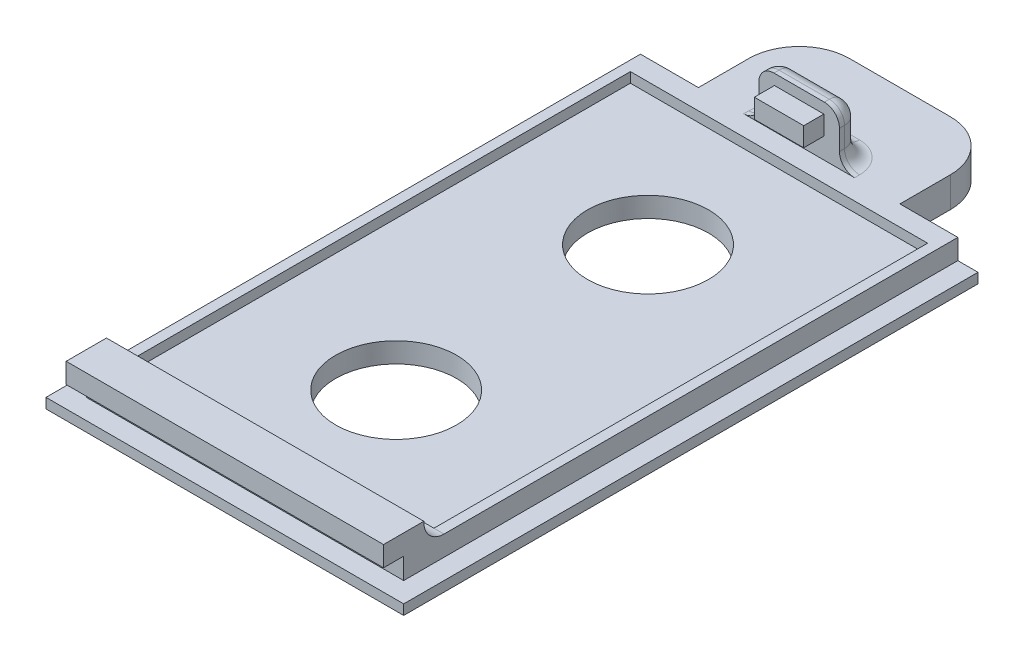
SolidWorks part; units mm, degrees
ref_plane "Plan de face" through (0, 0, 0) normal (0, 0, 1) x (1, 0, 0)
ref_plane "Plan de dessus" through (0, 0, 0) normal (0, 1, 0) x (1, 0, 0)
ref_plane "Plan de droite" through (0, 0, 0) normal (1, 0, 0) x (0, 0, -1)
sketch "Esquisse1" plane through (0, 0, 0) normal (0, 0, 1) x (1, 0, 0)
  line L0 (0, 0) -> (-2, 0)
  line L2 (0, 0) -> (0, 2)
  line L3 (0, 2) -> (31.5, 2)
  line L4 (31.5, 0) -> (31.5, 2)
  line L5 (-2, 0) -> (-2, -1)
  line L6 (-2, -1) -> (33.5, -1)
  line L7 (33.5, -1) -> (33.5, 0)
  line L8 (33.5, 0) -> (31.5, 0)
  dimension "D1" = 2
  dimension "D2" = 31.5
  dimension "D3" = 2
  dimension "D4" = 1
extrude "Boss.-Extru.1" add sketch "Esquisse1" along normal blind 55
sketch "Esquisse2" plane through (0, -1, 0) normal (0, -1, 0) x (1, 0, 0)
  line L0 (-2, 55) -> (-2, 0) construction
  line L1 (-2, 57) -> (33.5, 57)
  line L2 (-2, 57) -> (-2, 55)
  line L3 (-2, 55) -> (33.5, 55)
  line L4 (33.5, 57) -> (33.5, 55)
  line L5 (-2, 55) -> (33.5, 55) construction
  dimension "D1" = 2
extrude "Boss.-Extru.2" add sketch "Esquisse2" against normal blind 1
sketch "Esquisse3" plane through (0, 0, 0) normal (-1, 0, 0) x (0, 0, 1)
  line L0 (55, 2) -> (55, 2.1)
  line L1 (55, 2.1) -> (57, 2.1)
  line L2 (57, 2.1) -> (57, 4.1)
  line L3 (57, 4.1) -> (53, 4.1)
  line L4 (53, 4.1) -> (53, 2)
  line L5 (55, 2) -> (0, 2) construction
  line L6 (53, 2) -> (55, 2)
  line L7 (55, 2) -> (55, 0) construction
  dimension "D1" = 2
  dimension "D2" = 2
  dimension "D3" = 0.1
  dimension "D4" = 2
extrude "Boss.-Extru.3" add sketch "Esquisse3" against normal up to surface (31.5 mm away) up to face at (31.5, 1, 27.5)
sketch "Esquisse4" plane through (0, 0, 0) normal (0, 0, -1) x (-1, 0, 0)
  line L2 (-19.75, 0.5) -> (-19.75, 7)
  line L3 (-19.75, 7) -> (-11.75, 7)
  line L4 (-11.75, 0.5) -> (-11.75, 7)
  line L7 (-19.75, 0.5) -> (-11.75, 0.5)
  line L9 (-31.5, 2) -> (0, 2) construction
  line L10 (-15.75, 0.5) -> (-15.75, -1) construction
  line L11 (2, -1) -> (-33.5, -1) construction
  dimension "D1" = 8
  dimension "D2" = 6.5
  dimension "D4" = 1.5
extrude "Boss.-Extru.4" add sketch "Esquisse4" along normal blind 2
sketch "Esquisse5" plane through (0, 0, 0) normal (0, 0, 1) x (1, 0, 0)
  line L0 (15.75, 5.95) -> (15.75, 7) construction
  line L1 (13.3, 5.95) -> (18.2, 5.95)
  line L2 (13.3, 5.95) -> (13.3, 4.05)
  line L3 (13.3, 4.05) -> (18.2, 4.05)
  line L4 (18.2, 5.95) -> (18.2, 4.05)
  line L5 (11.75, 7) -> (19.75, 7) construction
  line L6 (33.5, 0) -> (-2, 0) construction
  point P8 (13.3, 5)
  dimension "D1" = 1.9
  dimension "D2" = 4.9
  dimension "D3" = 5
extrude "Boss.-Extru.5" add sketch "Esquisse5" along normal blind 2
sketch "Esquisse6" plane through (0, -1, 0) normal (0, -1, 0) x (1, 0, 0)
  line L0 (5.75, 0) -> (5.75, -5)
  line L1 (-2, 0) -> (33.5, 0) construction
  line L2 (25.75, -5) -> (25.75, 0)
  line L3 (25.75, 0) -> (5.75, 0)
  line L4 (10.75, -10) -> (20.75, -10)
  arc A1 (20.75, -10) -> (25.75, -5) centre (20.75, -5) ccw
  arc A2 (10.75, -10) -> (5.75, -5) centre (10.75, -5) cw
  point P6 (15.75, 0)
  dimension "D2" = 5
  dimension "D1" = 5
  dimension "D3" = 20
extrude "Boss.-Extru.6" add sketch "Esquisse6" against normal up to surface (3 mm away) up to face at (15.75, 2, 17.6667)
sketch "Esquisse8" plane through (0, 2, 0) normal (0, 1, 0) x (1, 0, 0)
  line L0 (31.5, -53) -> (31.5, 0) construction
  line L1 (1, -51) -> (30.5, -51)
  line L2 (1, -51) -> (1, -2)
  line L3 (1, -2) -> (30.5, -2)
  line L4 (30.5, -51) -> (30.5, -2)
  line L5 (0, -55) -> (0, 0) construction
  line L6 (31.5, -53) -> (0, -53) construction
  line L7 (31.5, 0) -> (25.75, 0) construction
  dimension "D1" = 1
  dimension "D2" = 1
  dimension "D3" = 2
  dimension "D4" = 2
extrude "Enlèv. mat.-Extru.2" cut sketch "Esquisse8" against normal blind 1
fillet "Congé1" radius 2 1 edges at (15.75, 2, 53)
fillet "Congé4" radius 1.5 8 edges at (15.75, 2, -2) (15.75, 7, -2) (11.75, 2, -1) (11.75, 7, -1) (11.75, 4.5, -2) (19.75, 7, -1) (19.75, 4.5, -2) (19.75, 2, -1)
sketch "Esquisse7" plane through (0, 2, 0) normal (0, 1, 0) x (1, 0, 0)
  line L0 (15.75, -15) -> (15.75, 10) construction
  line L1 (15.75, -40) -> (15.75, -15) construction
  line L2 (20.75, 10) -> (10.75, 10) construction
  line L3 (15.75, -27.5) -> (31.5, -27.5) construction
  line L4 (31.5, -55) -> (31.5, 0) construction
  circle A0 centre (15.75, -15) radius 6
  circle A1 centre (15.75, -40) radius 6
  point P4 (15.75, -27.5)
  dimension "D2" = 12
  dimension "D1" = 25
extrude "Enlèv. mat.-Extru.1" cut sketch "Esquisse7" against normal through all
